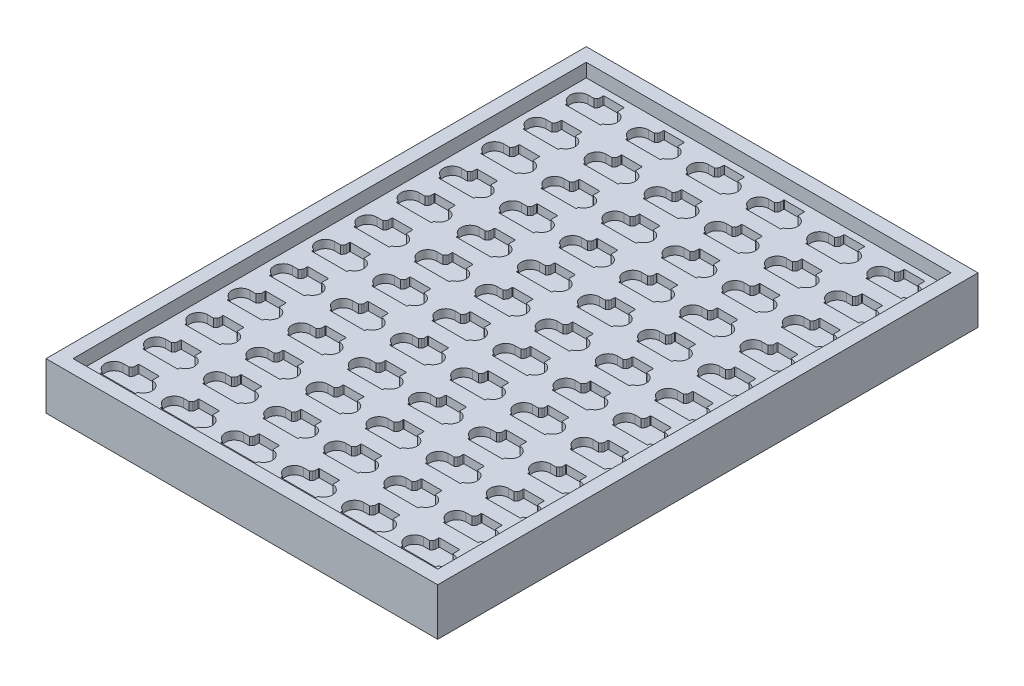
SolidWorks part; units mm, degrees
ref_plane "Front Plane" through (0, 0, 0) normal (0, 0, 1) x (1, 0, 0)
ref_plane "Top Plane" through (0, 0, 0) normal (0, 1, 0) x (1, 0, 0)
ref_plane "Right Plane" through (0, 0, 0) normal (1, 0, 0) x (0, 0, -1)
sketch "Sketch1" plane through (0, 0, 0) normal (0, 1, 0) x (1, 0, 0)
  line L1 (-145, 200) -> (145, 200)
  line L2 (-145, 200) -> (-145, -200)
  line L3 (-145, -200) -> (145, -200)
  line L4 (145, 200) -> (145, -200)
  line L5 (-145, 200) -> (145, -200) construction
  line L6 (-145, -200) -> (145, 200) construction
  point P0 (0, 0)
  dimension "D1" = 290
  dimension "D2" = 400
extrude "Boss-Extrude1" add sketch "Sketch1" along normal blind 35
sketch "Sketch2" plane through (0, 35, 0) normal (0, 1, 0) x (1, 0, 0)
  line L0 (145, -200) -> (145, 200) construction
  line L1 (-145, -200) -> (145, -200) construction
  line L2 (-145, 200) -> (-145, -200) construction
  line L3 (145, 200) -> (-145, 200) construction
  line L4 (145, -200) -> (145, 200)
  line L5 (-145, -200) -> (145, -200)
  line L6 (-145, 200) -> (-145, -200)
  line L7 (145, 200) -> (-145, 200)
  line L8 (135, -190) -> (135, 190)
  line L9 (135, 190) -> (-135, 190)
  line L10 (-135, 190) -> (-135, -190)
  line L11 (-135, -190) -> (135, -190)
  dimension "D1" = 10
extrude "Cut-Extrude2" cut sketch "Sketch2" against normal blind 10 contours L8 L9 L10 L11
sketch "Sketch3" plane through (0, 25, 0) normal (0, 1, 0) x (1, 0, 0)
  line L0 (0, 211.8692) -> (0, -222.8207) construction
  line L1 (-219.8723, 0) -> (201.339, 0) construction
  line L2 (135, 190) -> (-135, 190) construction
  line L3 (135, 190) -> (-135, 190) construction
  line L4 (135, 185) -> (-135, 185) construction
  line L5 (135, 165) -> (-135, 165) construction
  line L6 (-135, 190) -> (-135, -190) construction
  line L7 (-135, 190) -> (-135, -190) construction
  line L8 (-130, 190) -> (-130, -190) construction
  line L9 (-95, 190) -> (-95, -190) construction
  line L10 (-112.5, 190) -> (-112.5, -190) construction
  line L11 (-117.13, 185) -> (-101.75, 185)
  line L13 (-139, 190) -> (-139, -190)
  line L15 (-101.75, 199.739) -> (-101.75, 174.9169) construction
  line L16 (-99.4062, 166.62) -> (-99.4062, 165)
  line L17 (-101.75, 179.7) -> (-101.75, 185)
  line L18 (-125.5938, 165) -> (-99.4062, 165)
  line L19 (-125.5938, 166.62) -> (-125.5938, 165)
  line L20 (-123.25, 179.7) -> (-118.8793, 179.7)
  line L25 (-117.13, 185) -> (-117.13, 181.5)
  line L26 (-117.13, 181.5) -> (-118.8793, 179.7)
  line L61 (-117.13, 185) -> (-72.13, 185) construction
  arc A1 (-123.25, 179.7) -> (-125.5938, 166.62) centre (-123.25, 172.95) ccw
  arc A2 (-101.75, 179.7) -> (-99.4062, 166.62) centre (-101.75, 172.95) cw
  point P19 (0, 0)
  point P20 (135, 172.25)
  point P21 (-135, 173.09)
  point P24 (-126.7855, 190)
  point P25 (115.6811, -99.309)
  point P29 (0, 0)
  point P40 (-112.5, 165)
  dimension "D11" = 2.51
  dimension "D9" = 13.5
  dimension "D12" = 3.5
  dimension "D6" = 5.3
  dimension "D7" = 1.62
  dimension "D13" = 45
  dimension "D3" = 5
  dimension "D4" = 35
  dimension "D5" = 17.5
  dimension "D8" = 26.5
extrude "Cut-Extrude3" cut sketch "Sketch3" against normal blind 6 contours A2 L17 L11 L25 L26 L20 A1 L19 L18 L16 region at (-112.0602, 25, -173.939)
fillet "Fillet2" radius 2 1 edges at (-117.13, 22, -181.5)
fillet "Fillet4" radius 0.5 1 edges at (-125.5938, 22, -166.62)
fillet "Fillet5" radius 0.5 1 edges at (-99.4062, 22, -166.62)
fillet "Fillet6" radius 0.5 1 edges at (-101.75, 22, -179.7)
fillet "Fillet7" radius 0.5 1 edges at (-101.75, 22, -185)
fillet "Fillet8" radius 0.5 1 edges at (-117.13, 22, -185)
fillet "Fillet9" radius 0.5 2 edges at (-125.5938, 22, -165) (-99.4062, 22, -165)
pattern_linear "LPattern4" count 6 spacing 44.5 along (1, 0, 0) count 12 spacing 31.3 along (0, 0, 1) of "Cut-Extrude3", "Fillet2", "Fillet4", "Fillet5", "Fillet6", "Fillet7", "Fillet8", "Fillet9"
